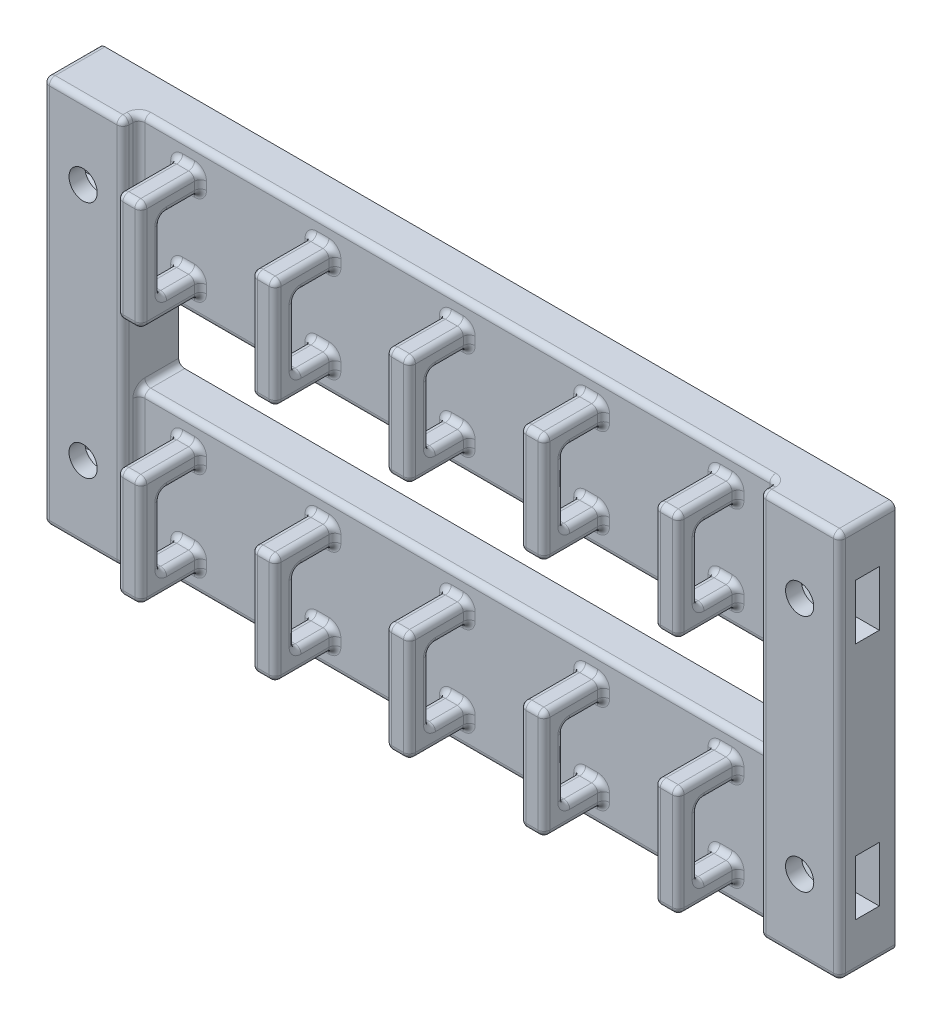
SolidWorks part; units mm, degrees
ref_plane "Front Plane" through (0, 0, 0) normal (0, 0, 1) x (1, 0, 0)
ref_plane "Top Plane" through (0, 0, 0) normal (0, 1, 0) x (1, 0, 0)
ref_plane "Right Plane" through (0, 0, 0) normal (1, 0, 0) x (0, 0, -1)
sketch "Sketch2" plane through (0, 0, 0) normal (0, 0, 1) x (1, 0, 0)
  line L1 (0, 0) -> (101.6, 0)
  line L2 (0, 0) -> (0, 19.05)
  line L3 (0, 19.05) -> (101.6, 19.05)
  line L4 (101.6, 0) -> (101.6, 19.05)
  dimension "D1" = 101.6
  dimension "D2" = 19.05
extrude "Boss-Extrude1" add sketch "Sketch2" along normal blind 5.08
ref_plane "Plane2" through (16.51, 0, 0) normal (-1, 0, 0) x (0, 0, 1)
sketch "Sketch6" plane through (16.51, 0, 0) normal (-1, 0, 0) x (0, 0, 1)
  line L0 (5.08, 16.51) -> (12.7, 16.51)
  line L1 (12.7, 16.51) -> (12.7, 2.54)
  line L2 (12.7, 2.54) -> (5.08, 2.54)
  line L3 (5.08, 19.05) -> (5.08, 0) construction
  line L4 (5.08, 2.54) -> (5.08, 5.08)
  line L5 (5.08, 5.08) -> (10.16, 5.08)
  line L6 (10.16, 5.08) -> (10.16, 13.97)
  line L7 (10.16, 13.97) -> (5.08, 13.97)
  line L8 (5.08, 13.97) -> (5.08, 16.51)
  line L9 (5.08, 19.05) -> (0, 19.05) construction
  point P2 (5.08, 9.525)
  point P11 (10.16, 9.525)
  dimension "D1" = 2.54
  dimension "D2" = 2.54
  dimension "D3" = 2.54
  dimension "D4" = 5.08
extrude "Boss-Extrude3" add sketch "Sketch6" along normal blind 1.524 and the other way blind 1.524
fillet "Fillet2" radius 0.762 24 edges at (16.51, 16.51, 5.08) (16.51, 2.54, 5.08) (16.51, 5.08, 5.08) (16.51, 13.97, 5.08) (16.51, 13.97, 10.16) (16.51, 5.08, 10.16) (18.034, 13.97, 7.62) (18.034, 9.525, 10.16) (18.034, 5.08, 7.62) (18.034, 3.81, 5.08) (18.034, 2.54, 8.89) (18.034, 9.525, 12.7) (18.034, 16.51, 8.89) (18.034, 15.24, 5.08) (14.986, 16.51, 8.89) (14.986, 9.525, 12.7) (14.986, 2.54, 8.89) (14.986, 3.81, 5.08) (14.986, 5.08, 7.62) (14.986, 9.525, 10.16) (14.986, 13.97, 7.62) (14.986, 15.24, 5.08) (16.51, 2.54, 12.7) (16.51, 16.51, 12.7)
pattern_linear "LPattern2" count 5 spacing 17.145 along (1, 0, 0) of "Boss-Extrude3", "Fillet2"
sketch "Sketch8" plane through (0, 0, 5.08) normal (0, 0, 1) x (1, 0, 0)
  line L0 (101.6, 19.05) -> (0, 19.05) construction
  line L1 (0, 0) -> (10.16, 0)
  line L2 (0, 0) -> (0, 19.05)
  line L3 (0, 19.05) -> (10.16, 19.05)
  line L4 (10.16, 0) -> (10.16, 19.05)
  line L6 (101.6, 0) -> (91.44, 0)
  line L7 (101.6, 0) -> (101.6, 19.05)
  line L8 (101.6, 19.05) -> (91.44, 19.05)
  line L9 (91.44, 0) -> (91.44, 19.05)
  dimension "D1" = 10.16
extrude "Boss-Extrude4" add sketch "Sketch8" along normal blind 2.032
hole_wizard "M3 Clearance Hole1" positions "Sketch3" profile "Sketch4" hole size "M3" standard "ANSI Metric" end condition through all
sketch "Sketch3" plane through (0, 0, 0) normal (0, 0, 1) x (1, 0, 0)
  line L0 (0, 19.05) -> (0, 0) construction
  line L1 (101.6, 0) -> (101.6, 19.05) construction
  line L2 (10.16, 0) -> (91.44, 0) construction
  point P0 (5.08, 9.525)
  point P2 (96.52, 9.525)
  dimension "D1" = 5.08
  dimension "D2" = 5.08
  dimension "D3" = 9.525
sketch "Sketch4" plane through (5.08, 9.525, 0) normal (1, 0, 0) x (0, 1, 0)
  line L0 (0, 0) -> (0, 12.7)
  line L1 (0, 12.7) -> (1.8, 12.7)
  line L2 (1.8, 12.7) -> (1.8, 0)
  line L5 (1.8, 0) -> (0, 0)
  line L11 (0, -6.35) -> (0, 107.95) construction
  dimension "Thru Hole Dia." = 3.6
  dimension "Thru Hole Depth" = 12.7
sketch "Sketch7" plane through (0, 0, 5.08) normal (0, 0, -1) x (-1, 0, 0)
  line L1 (-96.52, 6.0055) -> (-93.472, 7.7652)
  line L2 (-93.472, 7.7652) -> (-93.472, 11.2848)
  line L3 (-93.472, 11.2848) -> (-96.52, 13.0445)
  line L4 (-96.52, 13.0445) -> (-98.044, 12.1646) construction
  line L5 (-99.568, 11.2848) -> (-99.568, 9.525) construction
  line L6 (-98.044, 6.8854) -> (-96.52, 6.0055) construction
  line L7 (-96.52, 13.0445) -> (-101.6, 13.0445)
  line L8 (-8.128, 7.7652) -> (-5.08, 6.0055)
  line L9 (-5.08, 6.0055) -> (-3.556, 6.8854) construction
  line L10 (-2.032, 7.7652) -> (-2.032, 9.525) construction
  line L11 (-3.556, 12.1646) -> (-5.08, 13.0445) construction
  line L12 (-5.08, 13.0445) -> (-8.128, 11.2848)
  line L13 (-8.128, 11.2848) -> (-8.128, 7.7652)
  line L14 (-101.6, 0) -> (-101.6, 19.05) construction
  line L15 (-101.6, 13.0445) -> (-101.6, 6.0055)
  line L16 (-101.6, 6.0055) -> (-96.52, 6.0055)
  line L17 (-5.08, 13.0445) -> (0, 13.0445)
  line L18 (0, 19.05) -> (0, 0) construction
  line L19 (0, 13.0445) -> (0, 6.0055)
  line L20 (0, 6.0055) -> (-5.08, 6.0055)
  line L21 (-2.032, 11.2848) -> (-3.556, 12.1646) construction
  line L22 (-2.032, 9.525) -> (-2.032, 11.2848) construction
  line L23 (-3.556, 6.8854) -> (-2.032, 7.7652) construction
  line L24 (-99.568, 9.525) -> (-99.568, 7.7652) construction
  line L25 (-98.044, 12.1646) -> (-99.568, 11.2848) construction
  line L26 (-99.568, 7.7652) -> (-98.044, 6.8854) construction
  circle A0 centre (-96.52, 9.525) radius 3.048 construction
  circle A1 centre (-5.08, 9.525) radius 3.048 construction
  dimension "D1" = 6.096
extrude "Cut-Extrude1" cut sketch "Sketch7" along normal blind 3.048
pattern_linear "LPattern3" count 2 spacing 30.48 along (0, 1, 0) of bodies 107 108
sketch "Sketch9" plane through (0, 0, 0) normal (0, 0, -1) x (-1, 0, 0)
  line L0 (0, 30.48) -> (-101.6, 30.48) construction
  line L1 (-101.6, 19.05) -> (-91.44, 19.05)
  line L2 (-101.6, 19.05) -> (-101.6, 30.48)
  line L3 (-101.6, 30.48) -> (-91.44, 30.48)
  line L4 (-91.44, 19.05) -> (-91.44, 30.48)
  line L6 (-91.44, 19.05) -> (-91.44, 0) construction
  line L7 (0, 19.05) -> (-10.16, 19.05)
  line L8 (0, 19.05) -> (0, 30.48)
  line L9 (0, 30.48) -> (-10.16, 30.48)
  line L10 (-10.16, 19.05) -> (-10.16, 30.48)
  line L11 (-10.16, 0) -> (-10.16, 19.05) construction
extrude "Boss-Extrude5" add sketch "Sketch9" against normal blind 7.112
fillet "Fillet3" radius 0.762 28 edges at (50.8, 0, 5.08) (50.8, 19.05, 5.08) (10.16, 0, 6.096) (91.44, 0, 6.096) (10.16, 19.05, 2.54) (91.44, 19.05, 2.54) (10.16, 24.765, 7.112) (5.08, 0, 7.112) (0, 24.765, 7.112) (96.52, 0, 7.112) (91.44, 24.765, 7.112) (101.6, 24.765, 7.112) (10.16, 9.525, 5.08) (91.44, 9.525, 5.08) (0, 0, 3.556) (101.6, 0, 3.556) (5.08, 49.53, 7.112) (96.52, 49.53, 7.112) (10.16, 30.48, 2.54) (91.44, 30.48, 2.54) (10.16, 49.53, 6.096) (91.44, 49.53, 6.096) (50.8, 30.48, 5.08) (10.16, 40.005, 5.08) (50.8, 49.53, 5.08) (91.44, 40.005, 5.08) (101.6, 49.53, 3.556) (0, 49.53, 3.556)
